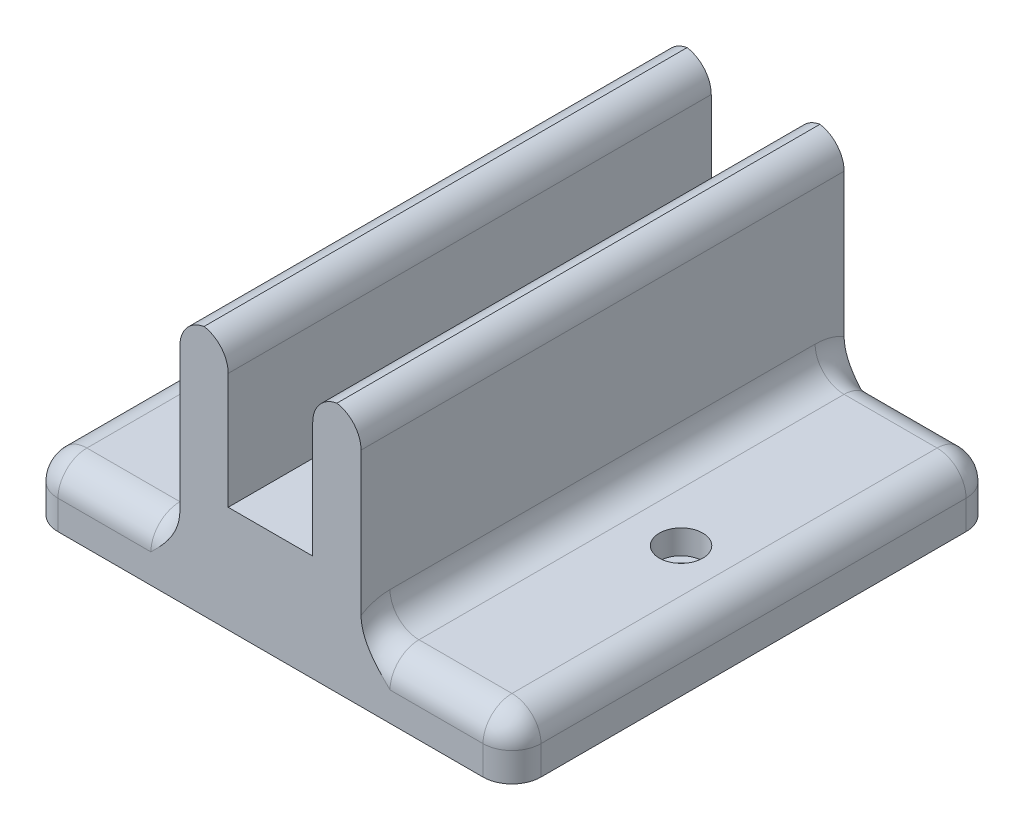
SolidWorks part; units mm, degrees
ref_plane "Front Plane" through (0, 0, 0) normal (0, 0, 1) x (1, 0, 0)
ref_plane "Top Plane" through (0, 0, 0) normal (0, 1, 0) x (1, 0, 0)
ref_plane "Right Plane" through (0, 0, 0) normal (1, 0, 0) x (0, 0, -1)
sketch "Sketch1" plane through (0, 0, 0) normal (0, 0, 1) x (1, 0, 0)
  line L0 (0, 0) -> (-37.5, 0)
  line L1 (-37.5, 0) -> (-37.5, 40)
  line L2 (-37.5, 40) -> (-27.5, 40)
  line L3 (-27.5, 40) -> (-27.5, 10)
  line L4 (-27.5, 10) -> (-10, 10)
  line L5 (-10, 10) -> (-10, 40)
  line L6 (-10, 40) -> (0, 40)
  line L7 (0, 40) -> (0, 0)
  dimension "D1" = 10
  dimension "D2" = 10
  dimension "D3" = 10
  dimension "D4" = 17.5
  dimension "D5" = 30
  dimension "D6" = 30
extrude "Boss-Extrude1" add sketch "Sketch1" along normal blind 100
sketch "Sketch2" plane through (0, 0, 0) normal (0, -1, 0) x (1, 0, 0)
  line L0 (-37.5, 100) -> (0, 0) construction
  line L1 (0, 100) -> (-37.5, 0) construction
  line L2 (-37.5, 100) -> (0, 100) construction
  line L3 (-68.75, 100) -> (31.25, 100)
  line L4 (-68.75, 100) -> (-68.75, 0)
  line L5 (-68.75, 0) -> (31.25, 0)
  line L6 (31.25, 100) -> (31.25, 0)
  line L7 (-68.75, 100) -> (31.25, 0) construction
  line L8 (-68.75, 0) -> (31.25, 100) construction
  point P8 (-18.75, 50)
  dimension "D1" = 0
  dimension "D2" = 100
extrude "Boss-Extrude2" add sketch "Sketch2" along normal blind 12
sketch "Sketch3" plane through (0, 0, 0) normal (0, 1, 0) x (1, 0, 0)
  line L0 (31.25, 0) -> (31.25, -100) construction
  line L1 (31.25, -100) -> (0, -100) construction
  line L2 (-37.5, -100) -> (-68.75, -100) construction
  line L3 (-68.75, -100) -> (-68.75, 0) construction
  circle A0 centre (16.25, -50) radius 4.5
  circle A1 centre (-53.75, -50) radius 4.5
  point P0 (16.25, -50)
  point P1 (-53.75, -50)
  dimension "D5" = 9
  dimension "D6" = 9
  dimension "D1" = 15
  dimension "D2" = 50
  dimension "D3" = 50
  dimension "D4" = 15
extrude "Cut-Extrude1" cut sketch "Sketch3" against normal blind 5
sketch "Sketch4" plane through (0, -5, 0) normal (0, 1, 0) x (1, 0, 0)
  circle A0 centre (16.25, -50) radius 2.65
  circle A1 centre (-53.75, -50) radius 2.65
  dimension "D1" = 5.3
  dimension "D2" = 5.3
extrude "Cut-Extrude2" cut sketch "Sketch4" against normal up to surface (7 mm away) up to face at (-18.75, -12, 50)
fillet "Fillet1" radius 6 14 edges at (31.25, -6, 0) (15.625, 0, 0) (31.25, 0, 50) (31.25, -6, 100) (15.625, 0, 100) (-53.125, 0, 100) (-68.75, -6, 100) (-68.75, -6, 0) (-53.125, 0, 0) (-68.75, 0, 50) (-10, 40, 50) (-27.5, 40, 50) (-37.5, 40, 50) (0, 40, 50)
fillet "Fillet3" radius 6 1 edges at (0, 0, 50) type face fillet first side face at (0, 9.7475, 50) second side face at (11.75, 0, 50)
fillet "Fillet4" radius 6 1 edges at (-37.5, 0, 50) type face fillet first side face at (-37.5, 9.7475, 50) second side face at (-58.25, 0, 50)
